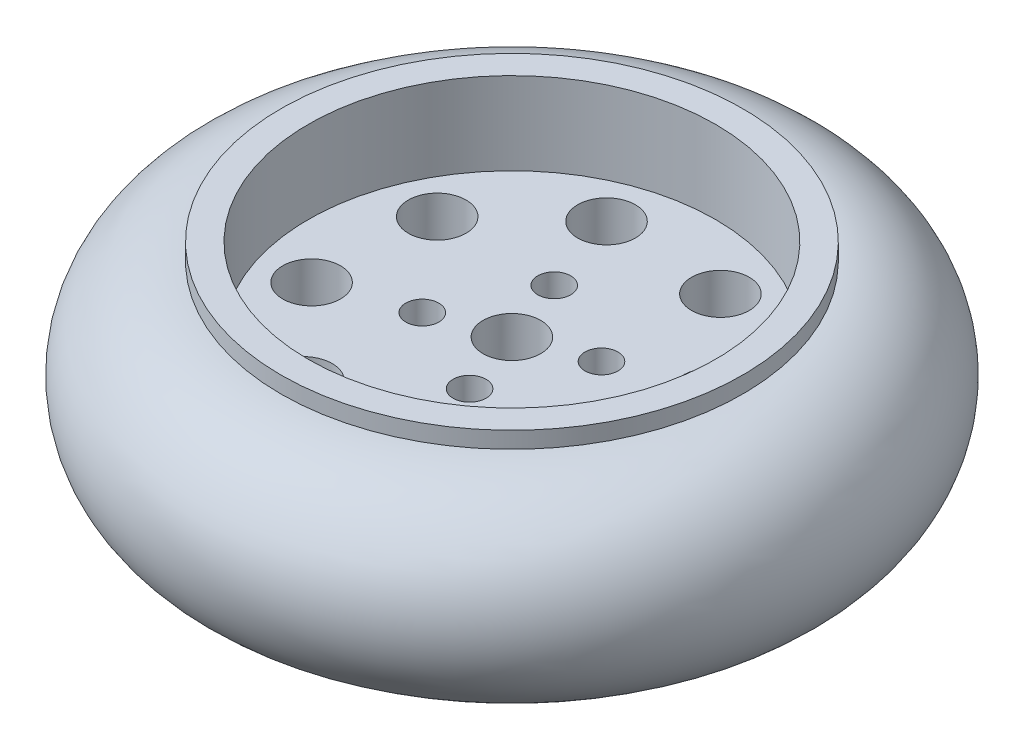
SolidWorks part; units mm, degrees
ref_plane "Plan de face" through (0, 0, 0) normal (0, 0, 1) x (1, 0, 0)
ref_plane "Plan de dessus" through (0, 0, 0) normal (0, 1, 0) x (1, 0, 0)
ref_plane "Plan de droite" through (0, 0, 0) normal (1, 0, 0) x (0, 0, -1)
sketch "Esquisse1" plane through (0, 0, 0) normal (0, 1, 0) x (1, 0, 0)
  circle A0 centre (0, 0) radius 40
  dimension "D1" = 80
extrude "Boss.-Extru.1" add sketch "Esquisse1" along normal blind 24
fillet "Congé2" 2 edges at (0, 24, 40) (0, 0, 40) type full round first side face at (0, 24, 40) second side face at (0, 0, 40) middle face at (0, 24, 40)
sketch "Esquisse2" plane through (0, 24, 0) normal (0, 1, 0) x (1, 0, 0)
  circle A0 centre (0, 0) radius 28 construction
  circle A1 centre (0, 0) radius 28
extrude "Enlèv. mat.-Extru.1" cut sketch "Esquisse2" against normal blind 8
sketch "Esquisse3" plane through (0, 0, 0) normal (0, -1, 0) x (1, 0, 0)
  circle A0 centre (0, 0) radius 28 construction
  circle A1 centre (0, 0) radius 28
extrude "Enlèv. mat.-Extru.2" cut sketch "Esquisse3" against normal blind 8
sketch "Esquisse4" plane through (0, 16, 0) normal (0, 1, 0) x (1, 0, 0)
  line L0 (0, 0) -> (-6.4085, 17.8866) construction
  circle A0 centre (0, 0) radius 3.5
  circle A1 centre (-2.867, 8.0019) radius 2
  circle A2 centre (8.0019, 2.867) radius 2
  circle A3 centre (2.867, -8.0019) radius 2
  circle A4 centre (-8.0019, -2.867) radius 2
  circle A5 centre (-6.4085, 17.8866) radius 3.5
  circle A6 centre (8.1162, 17.1793) radius 3.5
  circle A7 centre (17.8866, 6.4085) radius 3.5
  circle A8 centre (17.1793, -8.1162) radius 3.5
  circle A9 centre (6.4085, -17.8866) radius 3.5
  circle A10 centre (-8.1162, -17.1793) radius 3.5
  circle A11 centre (-17.8866, -6.4085) radius 3.5
  circle A12 centre (-17.1793, 8.1162) radius 3.5
  point P14 (0, 0)
  point P31 (0, 0)
  dimension "D1" = 7
  dimension "D2" = 4
  dimension "D5" = 7
  dimension "D3" = 8.5
  dimension "D6" = 10.5
  dimension "D4" = 4
  dimension "D7" = 8
extrude "Enlèv. mat.-Extru.3" cut sketch "Esquisse4" against normal through all
sketch "Esquisse5" plane through (0, 16, 0) normal (0, 1, 0) x (1, 0, 0)
  circle A0 centre (0, 0) radius 24.6987
  circle A1 centre (0, 0) radius 28 construction
  circle A2 centre (0, 0) radius 28
extrude "Boss.-Extru.2" add sketch "Esquisse5" along normal blind 10
